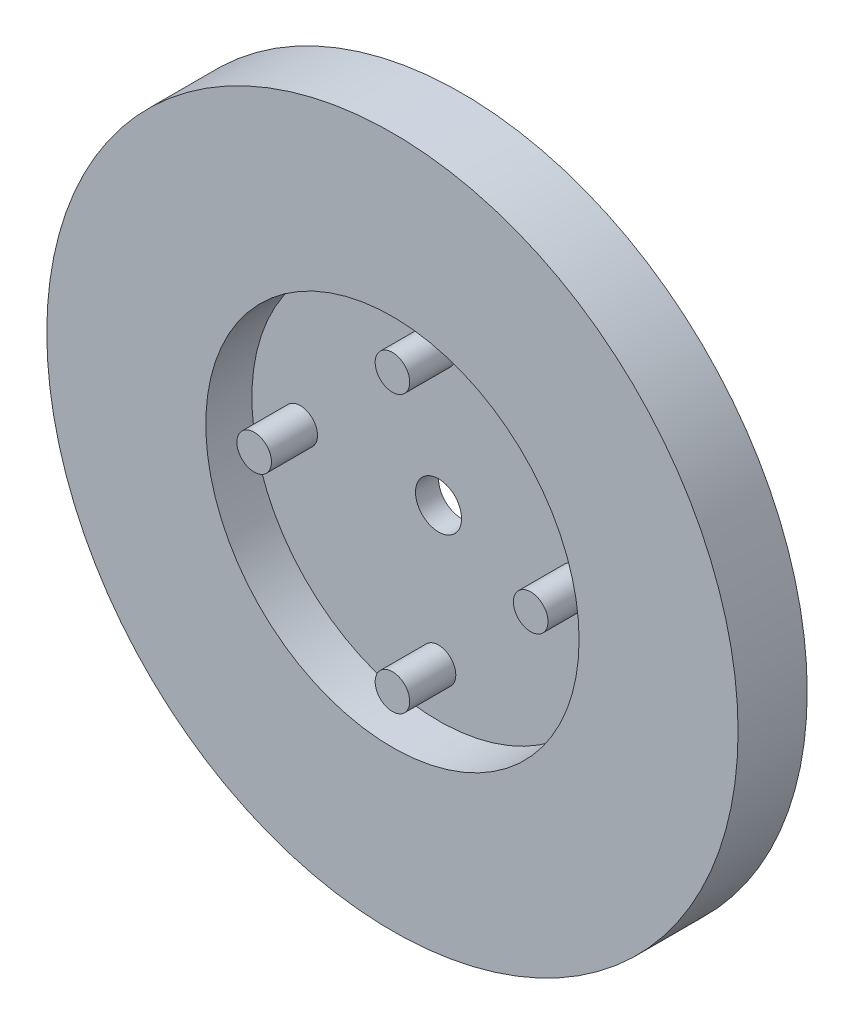
SolidWorks part; units mm, degrees
ref_plane "Front Plane" through (0, 0, 0) normal (0, 0, 1) x (1, 0, 0)
ref_plane "Top Plane" through (0, 0, 0) normal (0, 1, 0) x (1, 0, 0)
ref_plane "Right Plane" through (0, 0, 0) normal (1, 0, 0) x (0, 0, -1)
sketch "Sketch1" plane through (0, 0, 0) normal (0, 0, 1) x (1, 0, 0)
  circle A0 centre (0, 0) radius 6 construction
  circle A1 centre (0, 6) radius 0.75
  circle A2 centre (6, 0) radius 0.75
  circle A3 centre (0, -6) radius 0.75
  circle A4 centre (-6, 0) radius 0.75
  circle A5 centre (0, 0) radius 1
  circle A6 centre (0, 0) radius 8.1
  circle A7 centre (0, 0) radius 15
  point P14 (0, 0)
  point P15 (0, 0)
  dimension "D1" = 12
  dimension "D2" = 1.5
  dimension "D4" = 2
  dimension "D5" = 16.2
  dimension "D6" = 30
  dimension "D3" = 4
extrude "Boss-Extrude1" add sketch "Sketch1" along normal blind 1 contours A6 A1 A2 A3 A4 A5 | A1 | A4 | A2 | A3 region at (0, 6, 0) region at (6, 0, 0) region at (0, -6, 0) region at (-6, 0, 0) region at (-7.8709, 0, 0)
extrude "Boss-Extrude2" add sketch "Sketch1<3>" along normal blind 3 contours A7 A6 | A4 | A1 | A2 | A3 region at (0, 6, 0) region at (-6, 0, 0) region at (-14.5757, 0, 0)
sketch "Sketch1<3>" plane through (0, 0, 0) normal (0, 0, 1) x (1, 0, 0) same geometry as "Sketch1"
